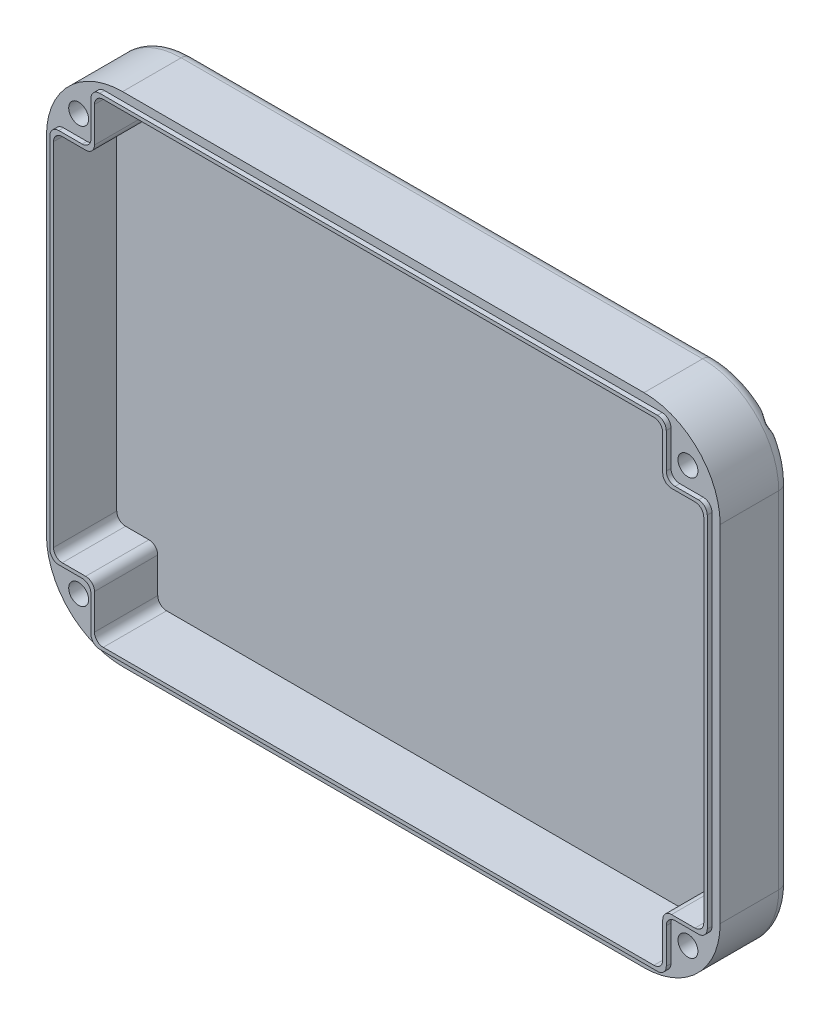
SolidWorks part; units mm, degrees
ref_plane "Спереди" through (0, 0, 0) normal (0, 0, 1) x (1, 0, 0)
ref_plane "Сверху" through (0, 0, 0) normal (0, 1, 0) x (1, 0, 0)
ref_plane "Справа" through (0, 0, 0) normal (1, 0, 0) x (0, 0, -1)
sketch "Sketch1" plane through (0, 0, 0) normal (0, 0, 1) x (1, 0, 0)
  line L1 (-57.5, 85) -> (57.5, 85) construction
  line L2 (-57.5, 85) -> (-57.5, 0) construction
  line L3 (-57.5, 0) -> (57.5, 0) construction
  line L5 (-57.5, 42.5) -> (22.5, 42.5) construction
  line L7 (0, 0) -> (0, 85) construction
  line L10 (-57.5, 85) -> (-57.5, 0) construction
  line L11 (-57.5, 85) -> (57.5, 85)
  line L12 (57.5, 85) -> (57.5, 0) construction
  line L13 (57.5, 0) -> (-57.5, 0)
  line L20 (57.5, 0) -> (57.5, 19)
  line L21 (57.5, 19) -> (57.5, 85)
  line L22 (-57.5, 0) -> (-57.5, 19)
  line L23 (-57.5, 19) -> (-57.5, 85)
  dimension "D1" = 115
  dimension "D2" = 85
extrude "Boss-Extrude1" add sketch "Sketch1" along normal blind 12
shell "Shell1" thickness 2 removed face at (0, 42.5, 12)
sketch "Sketch3" plane through (0, 0, 2) normal (0, 0, 1) x (1, 0, 0)
  line L0 (0, 0) -> (0, 85) construction
  line L1 (55.5, 2) -> (48.5, 2)
  line L2 (55.5, 2) -> (55.5, 11)
  line L3 (55.5, 11) -> (48.5, 11)
  line L4 (48.5, 2) -> (48.5, 11)
  line L5 (-57.5, 0) -> (57.5, 0) construction
  line L6 (57.5, 85) -> (-57.5, 85) construction
  line L7 (-48.5, 2) -> (-48.5, 11)
  line L8 (55.5, 2) -> (55.5, 83) construction
  line L9 (55.5, 42.5) -> (-55.5, 42.5) construction
  line L10 (-55.5, 83) -> (-55.5, 2) construction
  line L11 (-55.5, 11) -> (-48.5, 11)
  line L12 (-55.5, 2) -> (-55.5, 11)
  line L13 (-55.5, 2) -> (-48.5, 2)
  line L14 (-55.5, 83) -> (-48.5, 83)
  line L15 (-55.5, 83) -> (-55.5, 74)
  line L16 (-55.5, 74) -> (-48.5, 74)
  line L17 (-48.5, 83) -> (-48.5, 74)
  line L18 (48.5, 83) -> (48.5, 74)
  line L19 (55.5, 74) -> (48.5, 74)
  line L20 (55.5, 83) -> (55.5, 74)
  line L21 (55.5, 83) -> (48.5, 83)
  line L22 (57.5, 0) -> (57.5, 85) construction
  circle A0 centre (52, 7) radius 1.7
  circle A1 centre (-52, 7) radius 1.7
  circle A2 centre (-52, 78) radius 1.7
  circle A3 centre (52, 78) radius 1.7
  dimension "D3" = 3.4
  dimension "D1" = 7
  dimension "D2" = 9
  dimension "D4" = 7
  dimension "D5" = 5.5
extrude "Boss-Extrude3" add sketch "Sketch3" along normal up to surface (10 mm away) up to face at (0, 42.5, 12)
sketch "Sketch5" plane through (0, 0, 12) normal (0, 0, 1) x (1, 0, 0)
  line L0 (0, 0) -> (0, 85) construction
  line L1 (-57.5, 0) -> (57.5, 0) construction
  line L2 (57.5, 85) -> (-57.5, 85) construction
  line L4 (55.5, 11) -> (55.5, 74) construction
  line L5 (55.5, 42.5) -> (-55.5, 42.5) construction
  line L6 (55.5, 11) -> (55.5, 74) construction
  line L7 (56.1, 10.4) -> (56.1, 54.9886) construction
  line L8 (55.5, 11) -> (48.5, 11)
  line L9 (48.5, 11) -> (48.5, 2)
  line L10 (48.5, 2) -> (0, 2)
  line L11 (-48.5, 2) -> (48.5, 2) construction
  line L42 (55.5, 11) -> (55.5, 42.5)
  line L49 (56.1, 10.4) -> (49.1, 10.4)
  line L50 (49.1, 10.4) -> (49.1, 1.4)
  line L51 (49.1, 1.4) -> (0, 1.4)
  line L52 (-49.1, 1.4) -> (0, 1.4)
  line L53 (-49.1, 10.4) -> (-49.1, 1.4)
  line L54 (-56.1, 10.4) -> (-49.1, 10.4)
  line L58 (-55.5, 11) -> (-55.5, 42.5)
  line L61 (-48.5, 2) -> (0, 2)
  line L62 (-48.5, 11) -> (-48.5, 2)
  line L63 (-55.5, 11) -> (-48.5, 11)
  line L64 (-55.5, 74) -> (-48.5, 74)
  line L65 (-48.5, 74) -> (-48.5, 83)
  line L66 (-48.5, 83) -> (0, 83)
  line L68 (-55.5, 74) -> (-55.5, 42.5)
  line L70 (-56.1, 74.6) -> (-56.1, 10.4)
  line L71 (-56.1, 74.6) -> (-49.1, 74.6)
  line L72 (-49.1, 74.6) -> (-49.1, 83.6)
  line L73 (-49.1, 83.6) -> (0, 83.6)
  line L74 (49.1, 83.6) -> (0, 83.6)
  line L75 (49.1, 74.6) -> (49.1, 83.6)
  line L76 (56.1, 74.6) -> (49.1, 74.6)
  line L77 (56.1, 74.6) -> (56.1, 10.4)
  line L80 (55.5, 74) -> (55.5, 42.5)
  line L83 (48.5, 83) -> (0, 83)
  line L84 (48.5, 74) -> (48.5, 83)
  line L85 (55.5, 74) -> (48.5, 74)
  line L86 (42.6, -85.1835) -> (42.6, 29) construction
  line L87 (56.1, 54.9886) -> (42.6, -85.1835) construction
  line L88 (55.5, 42.5) -> (42, -97.6721) construction
  line L89 (42, -97.6721) -> (42, 29) construction
  line L90 (57.5, 85) -> (-57.5, 85) construction
  dimension "D1" = 42.5
  dimension "D2" = 0.6
extrude "Boss-Extrude4" add sketch "Sketch5" along normal blind 0.8
fillet "Fillet6" radius 1.5 12 edges at (-48.5, 2, 7.4) (-48.5, 11, 7.4) (-55.5, 11, 7.4) (-55.5, 74, 7.4) (-48.5, 74, 7.4) (-48.5, 83, 7.4) (48.5, 83, 7.4) (48.5, 74, 7.4) (55.5, 74, 7.4) (48.5, 2, 7.4) (55.5, 11, 7.4) (48.5, 11, 7.4)
fillet "Fillet7" radius 1.5 12 edges at (49.1, 10.4, 12.4) (49.1, 1.4, 12.4) (-49.1, 1.4, 12.4) (-49.1, 10.4, 12.4) (-56.1, 74.6, 12.4) (-49.1, 74.6, 12.4) (-49.1, 83.6, 12.4) (49.1, 83.6, 12.4) (49.1, 74.6, 12.4) (56.1, 74.6, 12.4) (-56.1, 10.4, 12.4) (56.1, 10.4, 12.4)
fillet "Fillet8" radius 13 4 edges at (-57.5, 0, 6) (-57.5, 85, 6) (57.5, 85, 6) (57.5, 0, 6)
fillet "Fillet11" radius 2 8 edges at (53.6924, 81.1924, 0) (57.5, 42.5, 0) (53.6924, 3.8076, 0) (0, 0, 0) (-53.6924, 3.8076, 0) (-57.5, 42.5, 0) (-53.6924, 81.1924, 0) (0, 85, 0)
ref_plane "Plane1" through (0, 42.5, 0) normal (0, -1, 0) x (-1, 0, 0)
ref_plane "Plane2" through (0, 0, 0) normal (1, 0, 0) x (0, 0, -1)
ref_plane "Plane3" through (0, 0, 7.5) normal (0, 0, 1) x (1, 0, 0)
sketch "Sketch17" plane through (0, 0, 0) normal (0, 0, -1) x (-1, 0, 0)
  line L0 (0, 0) -> (0, 85) construction
  line L2 (-44.5, 85) -> (44.5, 85) construction
  line L3 (0, 85) -> (55.5, 42.5) construction
  line L4 (55.5, 42.5) -> (-55.5, 42.5) construction
  line L5 (44.5, 0) -> (-44.5, 0) construction
  circle A0 centre (52, 7) radius 1.7
  circle A1 centre (-52, 7) radius 1.7
  circle A2 centre (-52, 78) radius 1.7
  circle A3 centre (52, 78) radius 1.7
  dimension "D1" = 3.4
extrude "Cut-Extrude5" cut sketch "Sketch17" against normal blind 10
sketch "Sketch18" plane through (0, 0, 0) normal (0, 0, -1) x (-1, 0, 0)
  line L0 (0, 0) -> (0, 85) construction
  line L1 (-57.5, 13) -> (-57.5, 72) construction
  line L2 (-44.5, 85) -> (44.5, 85) construction
  line L4 (57.5, 72) -> (57.5, 13) construction
  line L5 (57.5, 42.5) -> (-57.5, 42.5) construction
  circle A0 centre (52, 7) radius 2.5
  circle A1 centre (-52, 7) radius 2.5
  circle A2 centre (-52, 78) radius 2.5
  circle A3 centre (52, 78) radius 2.5
  dimension "D1" = 5
extrude "Cut-Extrude6" cut sketch "Sketch18" against normal blind 5
fillet "Fillet16" radius 0.4 8 edges at (-54.3011, 78.9773, 0.2862) (-53.4586, 4.9696, 0.2862) (-50.0478, 8.5617, 0) (54.3011, 6.0227, 0.2862) (50.0478, 76.4383, 0) (-50.0478, 76.4383, 0) (50.0478, 8.5617, 0) (53.4586, 80.0304, 0.2862)
ref_plane "Plane4" through (0, 19, 0) normal (0, -1, 0) x (-1, 0, 0)
ref_plane "Plane5" through (0, 0, 0) normal (1, 0, 0) x (0, 0, -1)
sketch "Sketch19" plane through (0, 0, 0) normal (0, 0, -1) x (-1, 0, 0)
  circle A0 centre (-9.6, 73.2) radius 1
  dimension "D1" = 2
  dimension "D2" = 1.155
extrude "Cut-Extrude7" cut sketch "Sketch19" against normal blind 10
